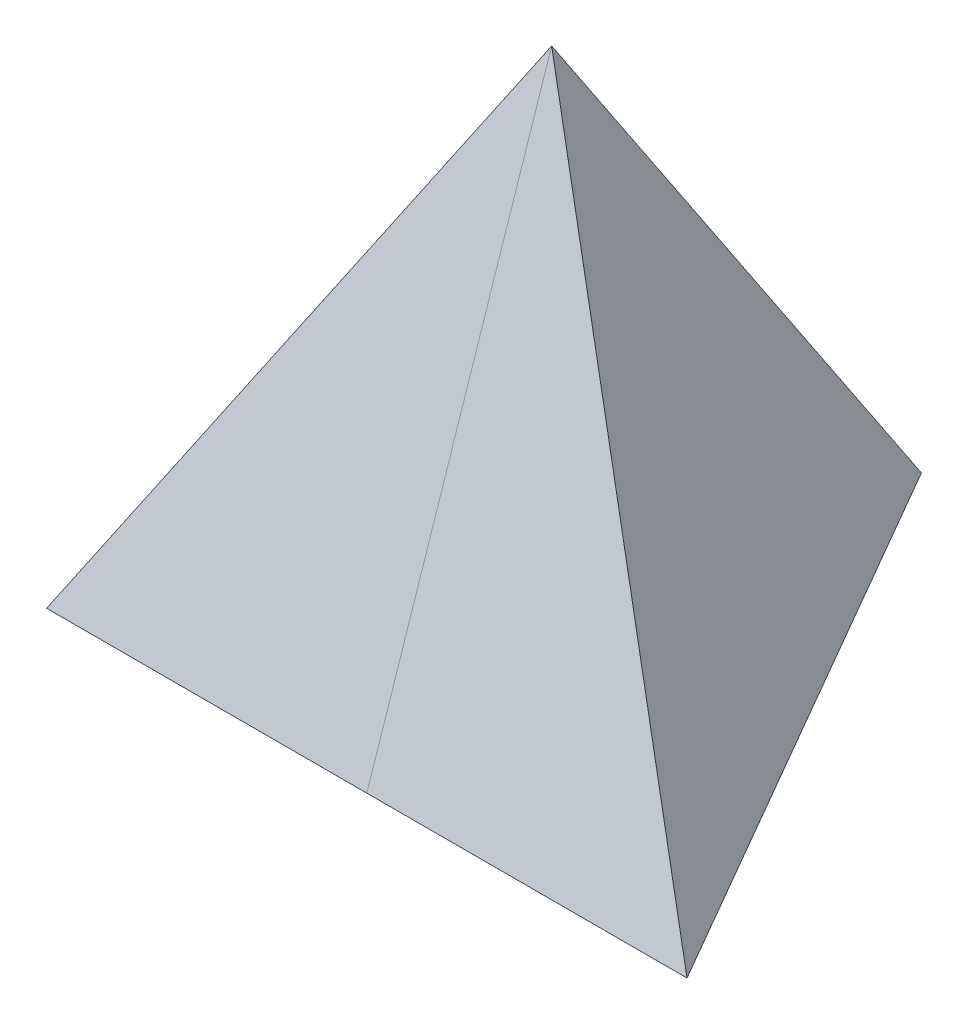
SolidWorks part; units mm, degrees
ref_plane "Front Plane" through (0, 0, 0) normal (0, 0, 1) x (1, 0, 0)
ref_plane "Top Plane" through (0, 0, 0) normal (0, 1, 0) x (1, 0, 0)
ref_plane "Right Plane" through (0, 0, 0) normal (1, 0, 0) x (0, 0, -1)
sketch "Sketch1" plane through (0, 0, 0) normal (0, 1, 0) x (1, 0, 0)
  line L0 (0, 33.8667) -> (0, -16.9333)
  line L1 (0, 33.8667) -> (-29.3294, -16.9333)
  line L2 (-29.3294, -16.9333) -> (29.3294, -16.9333) construction
  line L3 (29.3294, -16.9333) -> (0, 33.8667) construction
  line L4 (-29.3294, -16.9333) -> (0, -16.9333)
  circle A0 centre (0, 0) radius 16.9333 construction
  dimension "D1" = 50.8
ref_plane "Plane1" through (0, 50.8, 0) normal (0, 1, 0) x (1, 0, 0)
sketch "Sketch2" plane through (0, 50.8, 0) normal (0, 1, 0) x (1, 0, 0)
  point P0 (0, 0)
loft "Loft1" add profiles "Sketch1", "Sketch2"
sketch "Sketch3" plane through (0, 0, 0) normal (0, 1, 0) x (1, 0, 0)
  line L0 (0, 33.8667) -> (0, -16.9333)
  line L1 (0, 33.8667) -> (-29.3294, -16.9333) construction
  line L2 (-29.3294, -16.9333) -> (29.3294, -16.9333) construction
  line L3 (29.3294, -16.9333) -> (0, 33.8667)
  line L4 (0, -16.9333) -> (29.3294, -16.9333)
  circle A0 centre (0, 0) radius 16.9333 construction
  dimension "D1" = 50.8
loft "Loft2" add profiles "Sketch3", "Sketch2<2>"
sketch "Sketch2<2>" plane through (0, 50.8, 0) normal (0, 1, 0) x (1, 0, 0) same geometry as "Sketch2"
